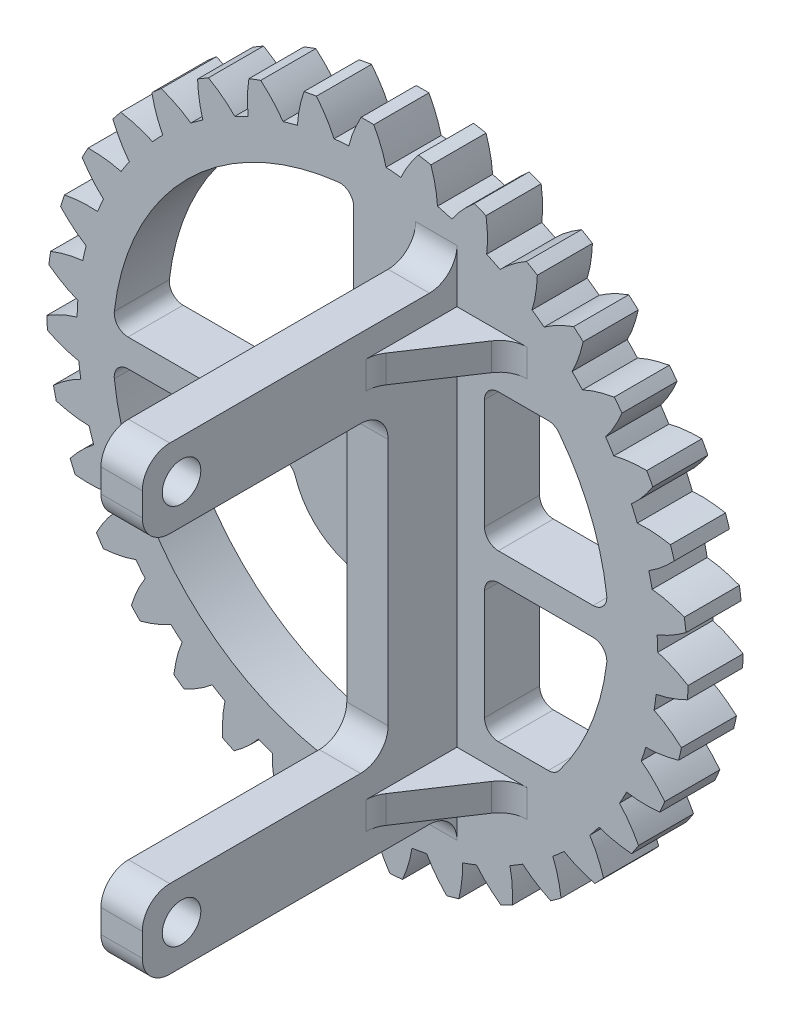
SolidWorks part; units mm, degrees
material "ABS"
ref_plane "Front Plane" through (0, 0, 0) normal (0, 0, 1) x (1, 0, 0)
ref_plane "Top Plane" through (0, 0, 0) normal (0, 1, 0) x (1, 0, 0)
ref_plane "Right Plane" through (0, 0, 0) normal (1, 0, 0) x (0, 0, -1)
sketch "Definition Drawing" plane through (0, 0, 0) normal (0, 0, 1) x (1, 0, 0)
  line L0 (23.2817, 0) -> (21.2817, 0) construction
  line L1 (0, 0) -> (-9.7013, 17.7112) construction
  line L2 (0, 0) -> (0, 23.2817) construction
  line L3 (0, 0) -> (1.4652, 20.1408) construction
  line L4 (-9.7013, 17.7112) -> (0.4602, 23.2771) construction
  line L5 (0, 0) -> (0.9497, 22.2614) construction
  line L6 (0, 0) -> (0.9997, 22.2593) construction
  line L7 (0, 0) -> (-7.07, 18.916) construction
  line L8 (-7.07, 18.916) -> (1.0696, 21.9582) construction
  line L9 (0, 0) -> (-4.2935, 19.7324) construction
  line L10 (-4.2935, 19.7324) -> (1.3671, 20.964) construction
  line L11 (0, 0) -> (-1.4288, 20.1435) construction
  line L12 (-1.4288, 20.1435) -> (1.4604, 20.3484) construction
  circle A0 centre (0, 0) radius 20.1941 construction
  circle A1 centre (0, 0) radius 21.2817 construction
  circle A2 centre (0, 0) radius 22.2817 construction
  circle A3 centre (0, 0) radius 23.2817 construction
  circle A4 centre (0, 0) radius 21.0817 construction
  arc A5 (0.9497, 22.2614) -> (0.9997, 22.2593) centre (0, 0) cw construction
  spline S0 degree 3 poles (1.4652, 20.1408) (1.4702, 20.4181) (1.2975, 21.5187) (0.8558, 22.5486) (0.4602, 23.2771) knots 0 0 0 0 0.250016 1 1 1 1 construction
  point P13 (22.2817, 0)
  dimension "D4" = 44.5634
  dimension "D5" = 40.3881
  dimension "D1" = 2
  dimension "D2" = 0.2
  dimension "D3" = 2.571
  dimension "D6" = 0.05
  dimension "D7" = 32.873
  dimension "D11" = 8.6895
  dimension "D12" = 5.793
  dimension "D13" = 2.8965
  dimension "D8" = 24.654
  dimension "D9" = 16.436
  dimension "D10" = 8.218
sketch "Sketch5" plane through (0, 0, 0) normal (0, 0, 1) x (1, 0, 0)
  circle A1 centre (0, 0) radius 21.0817
  circle A2 centre (0, 0) radius 1.5
  circle A3 centre (0, 0) radius 21.0817 construction
  dimension "D1" = 3
extrude "Extrude Body" add sketch "Sketch5" along normal mid plane 4
sketch "Sketch6" plane through (0, 0, 0) normal (0, 0, 1) x (1, 0, 0)
  line L0 (0, 23.2817) -> (0, 0) construction
  line L4 (1.4652, 20.1408) -> (0.1088, 1.496)
  line L5 (0, 0) -> (1.4652, 20.1408) construction
  line L6 (-1.4652, 20.1408) -> (-0.1088, 1.496)
  arc A0 (0.4602, 23.2771) -> (-0.4602, 23.2771) centre (0, 0) ccw
  arc A3 (0.1088, 1.496) -> (-0.1088, 1.496) centre (0, 0) ccw
  circle A4 centre (0, 0) radius 1.5 construction
  spline S0 degree 3 poles (1.4652, 20.1408) (1.4702, 20.4181) (1.2975, 21.5187) (0.8558, 22.5486) (0.4602, 23.2771) knots 0 0 0 0 0.250016 1 1 1 1
  spline S1 degree 3 poles (-1.4652, 20.1408) (-1.4702, 20.4181) (-1.2975, 21.5187) (-0.8558, 22.5486) (-0.4602, 23.2771) knots 0 0 0 0 0.250016 1 1 1 1
extrude "Extrude Tooth" add sketch "Sketch6" along normal mid plane 4
pattern_circular "CirPattern1" count 35 over 360 about axis through (0, 0, 2) along (0, 0, -1) of "Extrude Tooth" reverse direction yes
sketch "Sketch8" plane through (0, 0, 0) normal (0, 0, 1) x (1, 0, 0)
  line L6 (0, 23.2817) -> (0, 0) construction
  line L7 (0, 0) -> (23.2817, 0) construction
  line L8 (1.75, 16.3521) -> (1.75, 5.3327)
  line L9 (5.3327, 1.75) -> (16.3521, 1.75)
  circle A2 centre (0, 0) radius 23.2817 construction
  arc A20 (17.3382, 2.9158) -> (2.9158, 17.3382) centre (0, 0) ccw
  circle A21 centre (0, 0) radius 21.0817 construction
  arc A23 (16.3521, 1.75) -> (17.3382, 2.9158) centre (16.3521, 2.75) ccw
  arc A24 (5.3327, 1.75) -> (4.4439, 2.2917) centre (5.3327, 2.75) cw
  arc A25 (1.75, 5.3327) -> (2.2917, 4.4439) centre (2.75, 5.3327) ccw
  arc A26 (1.75, 16.3521) -> (2.9158, 17.3382) centre (2.75, 16.3521) cw
  arc A27 (4.4439, 2.2917) -> (2.2917, 4.4439) centre (0, 0) ccw
  circle A28 centre (0, 0) radius 1.5 construction
  dimension "D6" = 1
  dimension "D4" = 3.5
  dimension "D5" = 3.5
  dimension "D2" = 3.5
  dimension "D3" = 90
extrude "Cut Spoke" [suppressed] cut sketch "Sketch8" against normal through all and the other way through all
pattern_circular "Pattern Spokes" [suppressed] count 4 over 360 of bodies 133
ref_plane "Plane1" through (0, 0, 2) normal (0, 0, 1) x (1, 0, 0)
ref_plane "Plane2" through (5, 0, 0) normal (1, 0, 0) x (0, 0, -1)
sketch "Sketch9" plane through (5, 0, 0) normal (1, 0, 0) x (0, 0, -1)
  line L0 (-2, 16.7) -> (-24.85, 16.7)
  line L1 (-2, 25.5785) -> (-2, -25.5785) construction
  line L2 (-24.85, 16.7) -> (-24.85, 11)
  line L3 (-24.85, 11) -> (-7, 11)
  line L4 (-7, 11) -> (-7, -11)
  line L5 (-7, 0) -> (-2, 0) construction
  line L6 (-2, -16.7) -> (-2, 16.7)
  line L7 (-24.85, -16.7) -> (-24.85, -11)
  line L8 (-2, -16.7) -> (-24.85, -16.7)
  line L9 (-24.85, -11) -> (-7, -11)
  circle A0 centre (-22, 13.85) radius 1.4
  circle A1 centre (-22, 13.85) radius 2.85 construction
  circle A2 centre (-22, -13.85) radius 1.4
  dimension "D2" = 2.8
  dimension "D1" = 13.85
  dimension "D3" = 11
  dimension "D4" = 20
  dimension "D5" = 15
extrude "Boss-Extrude1" add sketch "Sketch9" along normal mid plane 3
ref_plane "Plane3" through (0, 13.85, 0) normal (0, -1, 0) x (-1, 0, 0)
sketch "Sketch10" plane through (0, 13.85, 0) normal (0, -1, 0) x (-1, 0, 0)
  line L0 (-6.5, -2) -> (-10.5, -2)
  line L1 (-25.5785, -2) -> (25.5785, -2) construction
  line L2 (-10.5, -2) -> (-6.5, -8)
  line L3 (-6.5, -24.85) -> (-6.5, -2) construction
  line L4 (-6.5, -8) -> (-6.5, -2)
  dimension "D1" = 6
  dimension "D2" = 4
extrude "Boss-Extrude2" add sketch "Sketch10" along normal mid plane 2
mirror "Mirror1" about plane through (0, 0, 0) normal (0, 1, 0) of "Boss-Extrude2"
fillet "Fillet1" radius 2 6 edges at (5, 16.7, 24.85) (5, 11, 24.85) (5, -11, 24.85) (5, -16.7, 24.85) (5, 11, 7) (5, -11, 7)
fillet "Fillet2" radius 2 6 edges at (5, 16.7, 2) (5, -16.7, 2) (10.5, 13.85, 2) (6.5, 13.85, 8) (6.5, -13.85, 8) (10.5, -13.85, 2)
sketch "Sketch11" plane through (0, 0, 2) normal (0, 0, 1) x (1, 0, 0)
  line L0 (0, 0) -> (0, 19.5) construction
  line L1 (0, 0) -> (-19.5, 0) construction
  line L2 (-19.5, 0) -> (-4.5, 0)
  line L3 (0, 19.5) -> (0, 4.5)
  line L4 (-1, 18.473) -> (-1, 5.4083)
  line L5 (-18.473, 1) -> (-5.4083, 1)
  line L6 (-18.473, -1) -> (-5.4083, -1)
  line L7 (-1, -18.473) -> (-1, -5.4083)
  circle A0 centre (0, 0) radius 19.5 construction
  circle A1 centre (0, 0) radius 4.5 construction
  circle A2 centre (0, 0) radius 1.5 construction
  arc A3 (-19.5, 0) -> (0, 19.5) centre (0, 0) cw
  arc A4 (-4.5, 0) -> (0, 4.5) centre (0, 0) cw
  arc A5 (-18.473, 1) -> (-1, 18.473) centre (0, 0) cw
  arc A6 (-5.4083, 1) -> (-1, 5.4083) centre (0, 0) cw
  arc A7 (-5.4083, -1) -> (-1, -5.4083) centre (0, 0) ccw
  arc A8 (-18.473, -1) -> (-1, -18.473) centre (0, 0) ccw
  dimension "D1" = 39
  dimension "D2" = 3
  dimension "D3" = 1
extrude "Cut-Extrude1" cut sketch "Sketch11" against normal through all contours A5 L4 A6 L5 | L6 A7 L7 A8
sketch "Sketch12" plane through (0, 0, 2) normal (0, 0, 1) x (1, 0, 0)
  line L0 (14.0801, 12) -> (7.5, 12) construction
  line L1 (7.5, 12) -> (7.5, 0) construction
  line L2 (7.5, 0) -> (18.5, 0) construction
  line L3 (6.5, 9) -> (6.5, -9) construction
  line L4 (13.6107, 11) -> (8.5, 11)
  line L5 (8.5, 11) -> (8.5, 1)
  line L6 (8.5, 1) -> (17.4714, 1)
  line L7 (8.5, -1) -> (17.4714, -1)
  line L8 (8.5, -11) -> (8.5, -1)
  line L9 (13.6107, -11) -> (8.5, -11)
  circle A0 centre (0, 0) radius 18.5 construction
  arc A1 (-1, 18.473) -> (-18.473, 1) centre (0, 0) ccw construction
  arc A2 (18.5, 0) -> (14.0801, 12) centre (0, 0) ccw construction
  arc A3 (17.4714, 1) -> (13.6107, 11) centre (0, 0) ccw
  arc A4 (17.4714, -1) -> (13.6107, -11) centre (0, 0) cw
  dimension "D1" = 12
  dimension "D2" = 1
  dimension "D3" = 1
extrude "Cut-Extrude2" cut sketch "Sketch12" against normal through all
fillet "Fillet3" radius 1 16 edges at (13.6107, -11, 0) (17.4714, -1, 0) (17.4714, 1, 0) (13.6107, 11, 0) (8.5, 11, 0) (8.5, -11, 0) (8.5, 1, 0) (8.5, -1, 0) (-1, -18.473, 0) (-18.473, -1, 0) (-1, -5.4083, 0) (-5.4083, -1, 0) (-1, 5.4083, 0) (-5.4083, 1, 0) (-18.473, 1, 0) (-1, 18.473, 0)
equation "\"nTeeth\"= 35"
equation "\"xThickness\"= 4"
equation "\"dShaft\"= 3"
equation "\"aPressure\"=25"
equation "\"pitch\"= 4"
equation "\"rHeight\"= 2"
equation "\"rClearance\"= 0.2"
equation "\"xClearance\"=0.05"
equation "\"rFillet\"= 1"
equation "\"nSpokes\"= int ( ( \"nTeeth\" - 1 ) / 10 ) + 1'rounds up"
equation "\"dPitch\"= \"nTeeth\" * \"pitch\" / pi"
equation "\"xWall\"= IIF ( \"nTeeth\" > 30 , \"nTeeth\" / 10 , 3 )"
equation "\"dBase\"= \"dPitch\" * cos ( \"aPressure\" )"
equation "\"rOuter\"= \"dPitch\" / 2 + \"rHeight\" / 2"
equation "\"xInvolute\"= sqr ( \"rOuter\" ^ 2 - ( \"dBase\" / 2 ) ^ 2 )"
equation "\"aInvolute\"= 360 * \"xInvolute\" / ( \"dBase\" / 2 ) / 2 / pi"
equation "\"D1@Definition Drawing\" = \"rHeight\""
equation "\"D2@Definition Drawing\" = \"rClearance\""
equation "\"D4@Definition Drawing\" = \"dPitch\""
equation "\"D6@Definition Drawing\" = \"xClearance\""
equation "\"D5@Definition Drawing\" = \"dBase\""
equation "\"D7@Definition Drawing\" = \"aInvolute\""
equation "\"D11@Definition Drawing\" = \"xInvolute\" * 0.75"
equation "\"D12@Definition Drawing\" = \"xInvolute\" * 0.5"
equation "\"D13@Definition Drawing\" = \"xInvolute\" * 0.25"
equation "\"D8@Definition Drawing\" = \"aInvolute\" * 0.75"
equation "\"D9@Definition Drawing\" = \"aInvolute\" * 0.5"
equation "\"D10@Definition Drawing\" = \"aInvolute\" * 0.25"
equation "\"D1@Extrude Body\"=\"xThickness\""
equation "\"D1@Sketch5\"=\"dShaft\""
equation "\"D3@Definition Drawing\" = 360 / \"nTeeth\" / 2 / 2"
equation "\"D5@Sketch8\"=\"xWall\""
equation "\"D1@Sketch8\"=\"xWall\""
equation "\"D4@Sketch8\"=\"xWall\""
equation "\"D6@Sketch8\"=\"rFillet\""
equation "\"D1@Pattern Spokes\" = \"nSpokes\""
equation "\"rHub\"= IIF ( \"xWall\" * \"nSpokes\" / 6 > \"xWall\" , \"xWall\" * \"nSpokes\" / 6 , \"xWall\" )"
equation "\"D2@Sketch8\"=\"rHub\""
equation "\"D3@Sketch8\"=360/\"nSpokes\""
equation "\"D1@Extrude Tooth\" = \"xThickness\""
equation "\"D1@CirPattern1\"=\"nTeeth\""
